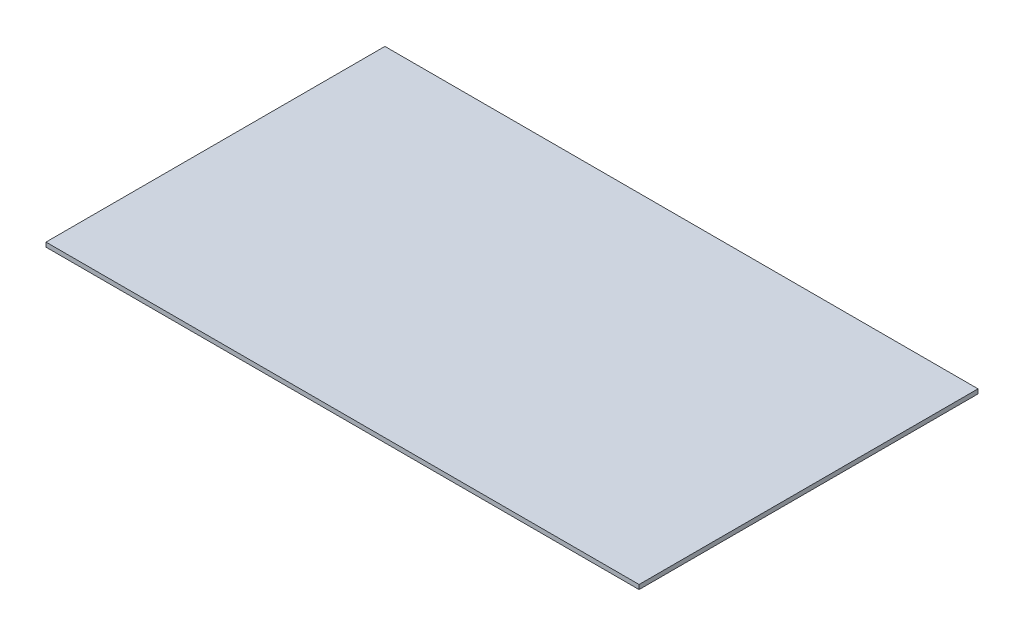
SolidWorks part; units mm, degrees
material "Plain Carbon Steel"
ref_plane "Front Plane" through (0, 0, 0) normal (0, 0, 1) x (1, 0, 0)
ref_plane "Top Plane" through (0, 0, 0) normal (0, 1, 0) x (1, 0, 0)
ref_plane "Right Plane" through (0, 0, 0) normal (1, 0, 0) x (0, 0, -1)
sketch "Sketch1" plane through (0, 0, 0) normal (0, 1, 0) x (1, 0, 0)
  line L1 (0, 0) -> (355.6, 0)
  line L2 (0, 0) -> (0, 203.2)
  line L3 (0, 203.2) -> (355.6, 203.2)
  line L4 (355.6, 0) -> (355.6, 203.2)
  dimension "D1" = 203.2
  dimension "D2" = 355.6
base flange "Base-Flange1" sketch "Sketch1" thickness 2.6568 reverse thickness direction no parameters "D1"=3.175
sketch "Sketch6" plane through (0, 0, 0) normal (0, 1, 0) x (1, 0, 0)
  line L0 (0, 101.6) -> (355.6, 101.6) construction
  line L1 (0, 203.2) -> (0, 0) construction
  line L2 (355.6, 0) -> (355.6, 203.2) construction
  line L3 (177.8, 203.2) -> (177.8, 0) construction
  line L4 (355.6, 203.2) -> (0, 203.2) construction
  line L5 (0, 0) -> (355.6, 0) construction
sketch "Sketch7" plane through (0, -2.6568, 0) normal (0, -1, 0) x (1, 0, 0)
  line L0 (0, -101.6) -> (355.9061, -101.6) construction
  line L1 (0, 0) -> (355.6, 0) construction
  dimension "D1" = 101.6
sketch "Bend-Lines1" [suppressed] plane through (0, 0, 0) normal (0, 1, 0) x (1, 0, 0)
sketch "Bounding-Box1" [suppressed] plane through (0, 0, 0) normal (0, 1, 0) x (1, 0, 0)
sheet metal parameters "Sheet-Metal1" thickness 2.6568 parameters "D1"=3.175
flat pattern "Flat-Pattern1" [suppressed]
sketch "Bend-Lines2" plane through (0, 0, 0) normal (0, 1, 0) x (1, 0, 0)
sketch3d "Bounding-Box2" [suppressed]
  line L0 (-355.6, 203.2, 0) -> (0, 203.2, 0) construction
  line L1 (-355.6, 0, 0) -> (0, 0, 0) construction
  line L2 (-355.6, 203.2, 0) -> (-355.6, 0, 0) construction
  line L3 (0, 203.2, 0) -> (0, 0, 0) construction
